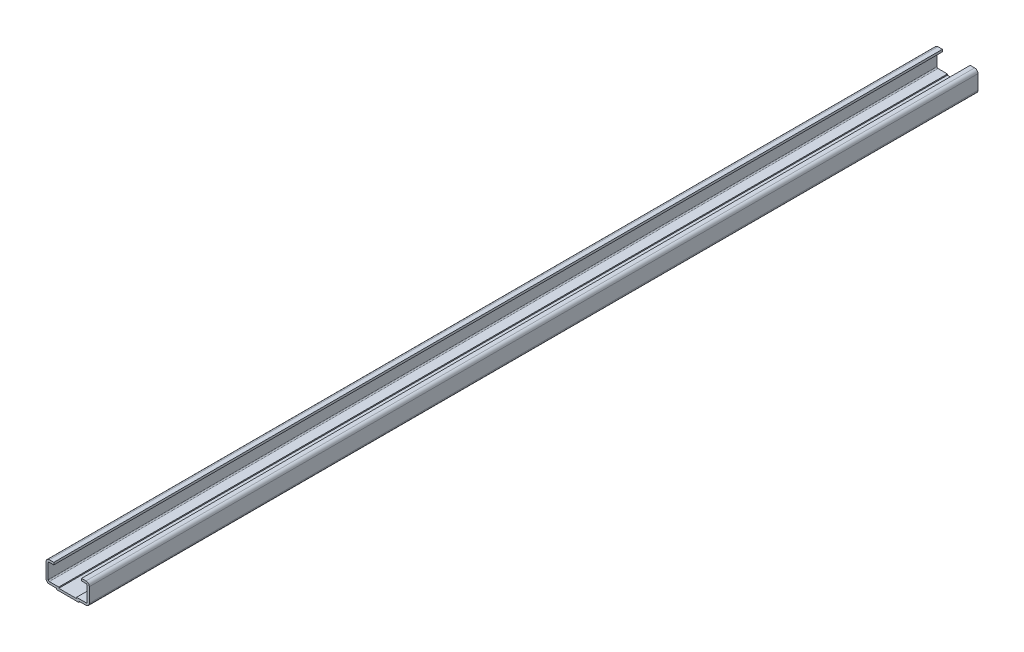
SolidWorks part; units mm, degrees
note: '?' marks a value the reader was unsure of.
ref_plane "Face" through (0, 0, 0) normal (0, 0, 1) x (1, 0, 0)
ref_plane "Dessus" through (0, 0, 0) normal (0, 1, 0) x (1, 0, 0)
ref_plane "Droite" through (0, 0, 0) normal (1, 0, 0) x (0, 0, -1)
sketch "Esquisse1" plane through (0, 0, 0) normal (0, 0, 1) x (1, 0, 0)
  line L0 (-5, 0) -> (5, 0)
  line L1 (9.75, 0.5) -> (9.75, 10)
  line L2 (9.75, 10) -> (6.25, 10)
  line L3 (9.75, 0.5) -> (5, 0.5)
  line L4 (5, 0) -> (5, 0.5)
  line L5 (0, 0) -> (0, 10.7996) construction
  line L6 (-5, 0) -> (-5, 0.5)
  line L7 (-9.75, 0.5) -> (-5, 0.5)
  line L8 (-9.75, 10) -> (-6.25, 10)
  line L9 (-9.75, 0.5) -> (-9.75, 10)
  point P9 (9.75, 0.5)
  point P12 (9.75, 10)
  dimension "D2" = 5
  dimension "D1" = 9.75
  dimension "D3" = 3.5
  dimension "D4" = 0.5
  dimension "D5" = 10
extrude "Base-Extru.-Mince" add sketch "Esquisse1" along normal blind 400 thin
fillet "Congé1" radius 1.5
fillet "Congé2" radius 0.5
ref_axis "Axe2" through (0, 1, 400) along (0, 0, -1)?
sketch "Esquisse3" plane through (-9.75, 0, 0) normal (1, 0, 0) x (0, 0, -1)
  line L0 (0, 2) -> (0, 8.5) construction
  line L2 (-417.5754, 4.5) -> (14.2281, 4.5) construction
  line L3 (0, 8.5) -> (-400, 8.5) construction
  line L4 (0, 0.5) -> (-400, 0.5) construction
  point P0 (-133.3333, 4.5)
  point P3 (-266.6667, 4.5)
  dimension "D1" = 133.3333
  dimension "D2" = 133.3333
